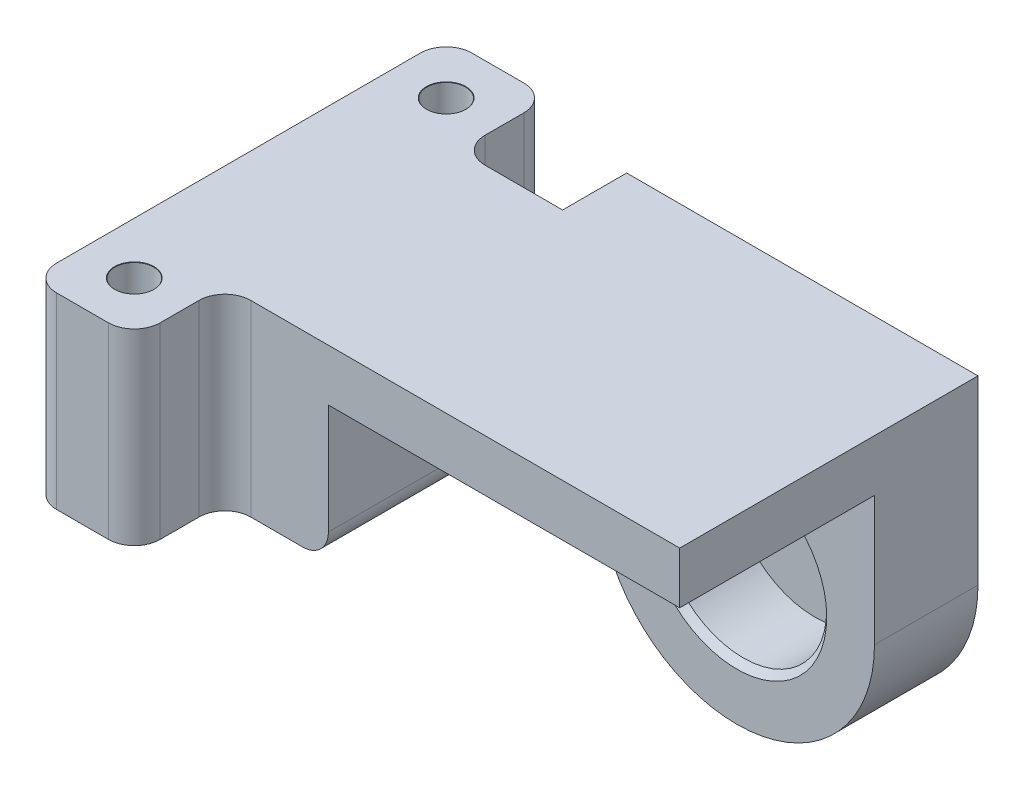
SolidWorks part; units mm, degrees
material "ABS"
ref_plane "Front Plane" through (0, 0, 0) normal (0, 0, 1) x (1, 0, 0)
ref_plane "Top Plane" through (0, 0, 0) normal (0, 1, 0) x (1, 0, 0)
ref_plane "Right Plane" through (0, 0, 0) normal (1, 0, 0) x (0, 0, -1)
sketch "Sketch1" plane through (0, 0, 0) normal (0, 1, 0) x (1, 0, 0)
  line L0 (0, 16.05) -> (0, -16.05)
  line L1 (0, -16.05) -> (8, -16.05)
  line L2 (8, -16.05) -> (8, -9.05)
  line L3 (8, -9.05) -> (43.15, -9.05)
  line L4 (43.15, -9.05) -> (43.15, 9.05)
  line L5 (43.15, 9.05) -> (8, 9.05)
  line L6 (8, 9.05) -> (8, 16.05)
  line L7 (8, 16.05) -> (0, 16.05)
  dimension "D1" = 32.1
  dimension "D2" = 8
  dimension "D3" = 7
  dimension "D4" = 35.15
extrude "Boss-Extrude1" add sketch "Sketch1" along normal blind 4
fillet "Fillet1" radius 2 6 edges at (0, 2, -16.05) (8, 2, -9.05) (8, 2, -16.05) (0, 2, 16.05) (8, 2, 16.05) (8, 2, 9.05)
hole_wizard "Ø3.0mm Dowel Hole1" positions "Sketch2" profile "Sketch3" hole size "Ø3.0" standard "ANSI Metric" end condition through all
sketch "Sketch2" plane through (0, 4, 0) normal (0, 1, 0) x (1, 0, 0)
  line L0 (4, 14.9464) -> (4, 9.6271) construction
  line L2 (0, 14.05) -> (0, -14.05) construction
  line L3 (8, 11.05) -> (8, 14.05) construction
  line L4 (6, 16.05) -> (2, 16.05) construction
  line L5 (2, -16.05) -> (6, -16.05) construction
  point P0 (4, 12.05)
  point P2 (4, -12.05)
  dimension "D1" = 4
  dimension "D2" = 4
sketch "Sketch3" plane through (4, 4, -12.05) normal (1, 0, 0) x (0, 0, 1)
  line L0 (0, 0) -> (0, 4)
  line L1 (0, 4) -> (1.5, 4)
  line L2 (1.5, 4) -> (1.5, 0.025)
  line L3 (1.5, 0.025) -> (1.525, 0)
  line L5 (1.525, 0) -> (0, 0)
  line L6 (-1.5, 0.025) -> (-1.525, 0) construction
  line L11 (0, -6.35) -> (0, 107.95) construction
  dimension "Thru Hole Dia." = 3
  dimension "Thru Hole Depth" = 4
  dimension "Near C'Sink Dia." = 3.05
  dimension "Near C'Sink Angle" = 90
sketch "Sketch21" plane through (0, 0, 0) normal (0, -1, 0) x (1, 0, 0)
  line L0 (16, 9.05) -> (16, -9.05)
  line L8 (0, 14.05) -> (0, -14.05)
  line L9 (2, -16.05) -> (6, -16.05)
  line L10 (8, -14.05) -> (8, -11.05)
  line L11 (10, -9.05) -> (43.15, -9.05)
  line L12 (43.15, -9.05) -> (43.15, 9.05)
  line L13 (43.15, 9.05) -> (10, 9.05)
  line L14 (8, 11.05) -> (8, 14.05)
  line L15 (6, 16.05) -> (2, 16.05)
  line L16 (0, 14.05) -> (0, -14.05)
  line L17 (2, -16.05) -> (6, -16.05)
  line L18 (8, -14.05) -> (8, -11.05)
  line L19 (10, -9.05) -> (16, -9.05)
  line L21 (16, 9.05) -> (10, 9.05)
  line L22 (8, 11.05) -> (8, 14.05)
  line L23 (6, 16.05) -> (2, 16.05)
  circle A0 centre (4, 12.05) radius 1.5
  circle A1 centre (4, -12.05) radius 1.5
  circle A2 centre (4, -12.05) radius 1.5 construction
  circle A3 centre (4, 12.05) radius 1.5 construction
  arc A6 (0, -14.05) -> (2, -16.05) centre (2, -14.05) ccw
  arc A7 (6, -16.05) -> (8, -14.05) centre (6, -14.05) ccw
  arc A8 (10, -9.05) -> (8, -11.05) centre (10, -11.05) ccw
  arc A9 (8, 11.05) -> (10, 9.05) centre (10, 11.05) ccw
  arc A10 (8, 14.05) -> (6, 16.05) centre (6, 14.05) ccw
  arc A11 (2, 16.05) -> (0, 14.05) centre (2, 14.05) ccw
  arc A12 (0, -14.05) -> (2, -16.05) centre (2, -14.05) ccw
  arc A13 (6, -16.05) -> (8, -14.05) centre (6, -14.05) ccw
  arc A14 (10, -9.05) -> (8, -11.05) centre (10, -11.05) ccw
  arc A15 (8, 11.05) -> (10, 9.05) centre (10, 11.05) ccw
  arc A16 (8, 14.05) -> (6, 16.05) centre (6, 14.05) ccw
  arc A17 (2, 16.05) -> (0, 14.05) centre (2, 14.05) ccw
  point P29 (0, 0)
  dimension "D2" = 16
  dimension "D1" = 0
extrude "Boss-Extrude4" add sketch "Sketch21" along normal blind 10.5
fillet "Fillet4" radius 2 1 edges at (16, -10.5, 0)
sketch "Sketch22" plane through (0, 0, -9.05) normal (0, 0, -1) x (-1, 0, 0)
  line L1 (-43.15, 4) -> (-16, 4)
  line L2 (-43.15, 4) -> (-43.15, 0)
  line L3 (-43.15, 0) -> (-16, 0)
  line L4 (-16, 4) -> (-16, 0)
extrude "Boss-Extrude5" add sketch "Sketch22" along normal blind 4.95
sketch "Sketch23" plane through (0, 0, -14) normal (0, 0, -1) x (-1, 0, 0)
  line L1 (-43.15, 0) -> (-21.87, 0)
  line L2 (-43.15, 0) -> (-43.15, -10)
  line L4 (-21.87, 0) -> (-21.87, -10)
  arc A0 (-43.15, -10) -> (-21.87, -10) centre (-32.51, -10) ccw
  dimension "D1" = 21.28
  dimension "D2" = 10
extrude "Boss-Extrude6" add sketch "Sketch23" against normal blind 8
sketch "Sketch24" plane through (0, 0, -6) normal (0, 0, 1) x (1, 0, 0)
  circle A0 centre (32.51, -10) radius 6.45
  arc A2 (21.87, -10) -> (43.15, -10) centre (32.51, -10) ccw construction
  dimension "D1" = 12.9
extrude "Cut-Extrude1" cut sketch "Sketch24" against normal blind 6
chamfer "Chamfer1" distance 0.5 angle 45 1 edges at (38.96, -10, -6)
